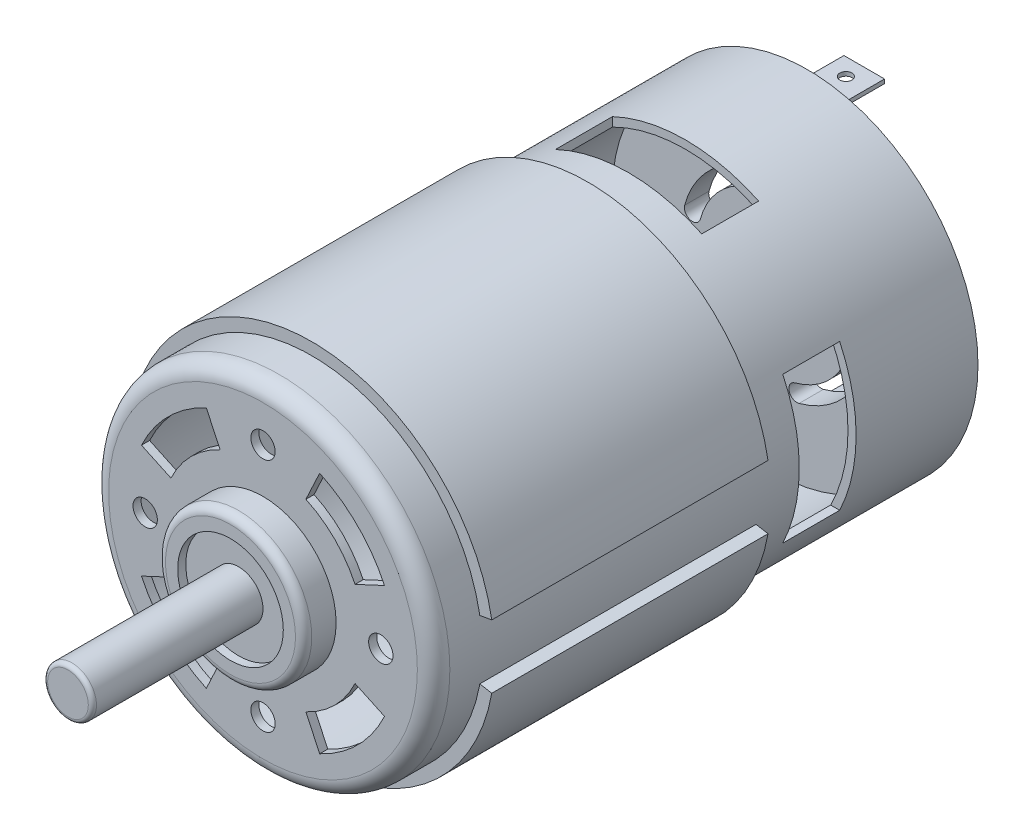
SolidWorks part; units mm, degrees
ref_plane "Front Plane" through (0, 0, 0) normal (0, 0, 1) x (1, 0, 0)
ref_plane "Top Plane" through (0, 0, 0) normal (0, 1, 0) x (1, 0, 0)
ref_plane "Right Plane" through (0, 0, 0) normal (1, 0, 0) x (0, 0, -1)
sketch "Sketch1" plane through (0, 0, 0) normal (0, 0, 1) x (1, 0, 0)
  circle A0 centre (0, 0) radius 21
  dimension "D1" = 42
extrude "Boss-Extrude1" add sketch "Sketch1" against normal blind 67
shell "Shell1" thickness 1 removed face at (21, 0, -67)
fillet "Fillet1" radius 2 1 edges at (21, 0, 0)
sketch "Sketch2" plane through (0, 0, 0) normal (0, 0, 1) x (1, 0, 0)
  line L0 (-19, 0) -> (19, 0) construction
  line L1 (11.3288, 5.2827) -> (13.1415, 6.128) construction
  line L2 (5.2827, 11.3288) -> (6.128, 13.1415) construction
  line L3 (11.3288, 5.2827) -> (14.9541, 6.9732)
  line L4 (5.2827, 11.3288) -> (6.9732, 14.9541)
  line L5 (11.3288, -5.2827) -> (14.9541, -6.9732)
  line L6 (5.2827, -11.3288) -> (6.9732, -14.9541)
  line L7 (-5.2827, -11.3288) -> (-6.9732, -14.9541)
  line L8 (-11.3288, -5.2827) -> (-14.9541, -6.9732)
  line L9 (-11.3288, 5.2827) -> (-14.9541, 6.9732)
  line L10 (-5.2827, 11.3288) -> (-6.9732, 14.9541)
  circle A0 centre (0, 0) radius 19 construction
  circle A1 centre (0, 0) radius 14.5 construction
  circle A2 centre (14.5, 0) radius 1.5
  circle A3 centre (0, -14.5) radius 1.5
  circle A4 centre (-14.5, 0) radius 1.5
  circle A5 centre (0, 14.5) radius 1.5
  arc A7 (11.3288, 5.2827) -> (5.2827, 11.3288) centre (0, 0) ccw
  arc A8 (5.2827, -11.3288) -> (11.3288, -5.2827) centre (0, 0) ccw
  circle A9 centre (0, 0) radius 12.5 construction
  arc A10 (14.9541, 6.9732) -> (6.9732, 14.9541) centre (0, 0) ccw
  arc A11 (6.9732, -14.9541) -> (14.9541, -6.9732) centre (0, 0) ccw
  arc A12 (-11.3288, -5.2827) -> (-5.2827, -11.3288) centre (0, 0) ccw
  arc A13 (-14.9541, -6.9732) -> (-6.9732, -14.9541) centre (0, 0) ccw
  arc A14 (-5.2827, 11.3288) -> (-11.3288, 5.2827) centre (0, 0) ccw
  arc A15 (-6.9732, 14.9541) -> (-14.9541, 6.9732) centre (0, 0) ccw
  point P7 (0, 0)
  point P20 (0, 0)
  point P42 (0, 0)
  dimension "D1" = 29
  dimension "D2" = 3
  dimension "D6" = 16.5
  dimension "D4" = 25
  dimension "D5" = 40
  dimension "D8" = 25
  dimension "D9" = 40
  dimension "D10" = 4
  dimension "D7" = 2
  dimension "D3" = 4
  dimension "D11" = 4
extrude "Cut-Extrude1" cut sketch "Sketch2" against normal up to next
sketch "Sketch3" plane through (0, 0, 0) normal (0, 0, 1) x (1, 0, 0)
  circle A0 centre (0, 0) radius 9
  dimension "D1" = 18
extrude "Boss-Extrude2" add sketch "Sketch3" along normal blind 4
fillet "Fillet2" radius 1 1 edges at (9, 0, 4)
sketch "Sketch4" plane through (0, 0, 4) normal (0, 0, 1) x (1, 0, 0)
  circle A0 centre (0, 0) radius 6.5
  dimension "D1" = 13
extrude "Cut-Extrude2" cut sketch "Sketch4" against normal blind 1
sketch "Sketch5" plane through (0, 0, 3) normal (0, 0, 1) x (1, 0, 0)
  circle A0 centre (0, 0) radius 3
  dimension "D1" = 6
extrude "Boss-Extrude3" add sketch "Sketch5" along normal blind 21
fillet "Fillet3" radius 0.5 1 edges at (3, 0, 24)
ref_plane "Plane1" through (0, 21, 0) normal (0, 1, 0) x (1, 0, 0)
sketch "Sketch6" plane through (0, 21, 0) normal (0, 1, 0) x (1, 0, 0)
  line L0 (21, 67) -> (-21, 67) construction
  line L1 (-9, 52) -> (9, 52)
  line L2 (-9, 52) -> (-9, 45)
  line L3 (-9, 45) -> (9, 45)
  line L4 (9, 52) -> (9, 45)
  line L5 (-9, 52) -> (9, 45) construction
  line L6 (-9, 45) -> (9, 52) construction
  line L7 (-21, 67) -> (-21, 2) construction
  point P0 (0, 48.5)
  dimension "D1" = 18
  dimension "D2" = 7
  dimension "D3" = 15
  dimension "D4" = 21
extrude "Cut-Extrude3" cut sketch "Sketch6" against normal up to surface (3.1394 mm away) up to face at (20, 0, -67)
pattern_circular "CirPattern1" count 4 over 360 about axis through (0, 0, -67) along (0, 0, 1) of "Cut-Extrude3"
sketch "Sketch7" plane through (0, 0, 0) normal (0, 0, 1) x (1, 0, 0)
  circle A0 centre (0, 0) radius 22.5
  circle A1 centre (0, 0) radius 21 construction
  circle A2 centre (0, 0) radius 21
  dimension "D1" = 45
extrude "Boss-Extrude4" add sketch "Sketch7" against normal blind 34 from offset 6 separate body offset against normal yes
sketch "Sketch9" plane through (0, 0, -6) normal (0, 0, 1) x (1, 0, 0)
  line L0 (0, 0) -> (22.5, 0) construction
  line L1 (20.681, 3.6466) -> (22.1582, 3.9071)
  line L2 (20.681, -3.6466) -> (22.1582, -3.9071)
  circle A0 centre (0, 0) radius 22.5 construction
  circle A1 centre (0, 0) radius 21 construction
  arc A2 (22.1582, -3.9071) -> (22.1582, 3.9071) centre (0, 0) ccw
  arc A3 (20.681, -3.6466) -> (20.681, 3.6466) centre (0, 0) ccw
  dimension "D1" = 10
  dimension "D2" = 10
  dimension "D3" = 1.5
  dimension "D4" = 1.5
extrude "Cut-Extrude4" cut sketch "Sketch9" against normal blind 34
sketch "Sketch10" plane through (0, 0, -67) normal (0, 0, -1) x (-1, 0, 0)
  circle A0 centre (0, 0) radius 20 construction
  circle A3 centre (0, 0) radius 20
extrude "Boss-Extrude5" add sketch "Sketch10" against normal blind 2 from offset 2 separate body offset against normal yes
sketch "Sketch11" plane through (0, 0, -65) normal (0, 0, -1) x (-1, 0, 0)
  circle A0 centre (0, 0) radius 15
  dimension "D1" = 30
extrude "Boss-Extrude6" add sketch "Sketch11" along normal blind 1
fillet "Fillet4" radius 1 1 edges at (-15, 0, -66)
sketch "Sketch12" plane through (0, 0, -66) normal (0, 0, -1) x (-1, 0, 0)
  circle A0 centre (0, 0) radius 7.5
  dimension "D1" = 15
extrude "Boss-Extrude7" add sketch "Sketch12" along normal blind 5
sketch "Sketch13" plane through (0, 0, -71) normal (0, 0, -1) x (-1, 0, 0)
  circle A0 centre (0, 0) radius 4
  dimension "D1" = 8
extrude "Boss-Extrude8" add sketch "Sketch13" along normal blind 2
sketch "Sketch14" plane through (0, 0, -73) normal (0, 0, -1) x (-1, 0, 0)
  circle A0 centre (0, 0) radius 3
  dimension "D1" = 6
extrude "Boss-Extrude9" add sketch "Sketch14" along normal blind 5
fillet "Fillet5" radius 0.5 1 edges at (-3, 0, -78)
fillet "Fillet6" radius 1 1 edges at (-4, 0, -71)
fillet "Fillet7" radius 1 1 edges at (-7.5, 0, -71)
sketch "Sketch15" plane through (0, 0, -66) normal (0, 0, -1) x (-1, 0, 0)
  line L0 (0, 0) -> (10.5, 0) construction
  line L1 (0, 0) -> (10.1422, 2.7176) construction
  line L2 (0, 0) -> (2.7176, 10.1422) construction
  arc A0 (10.1422, 2.7176) -> (2.7176, 10.1422) centre (0, 0) ccw construction
  circle A1 centre (0, 0) radius 10.5 construction
  circle A2 centre (10.5, 0) radius 1
  arc A3 (11.1081, 2.9764) -> (2.9764, 11.1081) centre (0, 0) ccw
  arc A4 (9.1763, 2.4588) -> (2.4588, 9.1763) centre (0, 0) ccw
  arc A5 (9.1763, 2.4588) -> (11.1081, 2.9764) centre (10.1422, 2.7176) ccw
  arc A6 (2.9764, 11.1081) -> (2.4588, 9.1763) centre (2.7176, 10.1422) ccw
  arc A7 (2.7176, -10.1422) -> (10.1422, -2.7176) centre (0, 0) ccw construction
  arc A8 (2.9764, -11.1081) -> (11.1081, -2.9764) centre (0, 0) ccw
  arc A9 (2.4588, -9.1763) -> (9.1763, -2.4588) centre (0, 0) ccw
  arc A10 (2.4588, -9.1763) -> (2.9764, -11.1081) centre (2.7176, -10.1422) ccw
  arc A11 (11.1081, -2.9764) -> (9.1763, -2.4588) centre (10.1422, -2.7176) ccw
  arc A12 (-10.1422, -2.7176) -> (-2.7176, -10.1422) centre (0, 0) ccw construction
  arc A13 (-11.1081, -2.9764) -> (-2.9764, -11.1081) centre (0, 0) ccw
  arc A14 (-9.1763, -2.4588) -> (-2.4588, -9.1763) centre (0, 0) ccw
  arc A15 (-9.1763, -2.4588) -> (-11.1081, -2.9764) centre (-10.1422, -2.7176) ccw
  arc A16 (-2.9764, -11.1081) -> (-2.4588, -9.1763) centre (-2.7176, -10.1422) ccw
  arc A17 (-2.7176, 10.1422) -> (-10.1422, 2.7176) centre (0, 0) ccw construction
  arc A18 (-2.9764, 11.1081) -> (-11.1081, 2.9764) centre (0, 0) ccw
  arc A19 (-2.4588, 9.1763) -> (-9.1763, 2.4588) centre (0, 0) ccw
  arc A20 (-2.4588, 9.1763) -> (-2.9764, 11.1081) centre (-2.7176, 10.1422) ccw
  arc A21 (-11.1081, 2.9764) -> (-9.1763, 2.4588) centre (-10.1422, 2.7176) ccw
  circle A22 centre (-10.5, 0) radius 1
  point P9 (7.4246, 7.4246)
  point P19 (7.4246, -7.4246)
  point P26 (-7.4246, -7.4246)
  point P33 (-7.4246, 7.4246)
  point P38 (0, 0)
  point P40 (0, 0)
  dimension "D1" = 21
  dimension "D2" = 2
  dimension "D5" = 1
  dimension "D3" = 15
  dimension "D4" = 75
  dimension "D6" = 4
  dimension "D7" = 2
extrude "Cut-Extrude5" cut sketch "Sketch15" against normal up to next (3 mm away)
sketch "Sketch16" plane through (0, 0, -65) normal (0, 0, -1) x (-1, 0, 0)
  line L0 (-4.5, 19.4872) -> (-4.5, 15.4872)
  line L1 (-4.5, 15.4872) -> (4.5, 15.4872)
  line L2 (4.5, 15.4872) -> (4.5, 19.4872)
  line L3 (4.5, -19.4872) -> (4.5, -15.4872)
  line L4 (4.5, -15.4872) -> (-4.5, -15.4872)
  line L5 (-4.5, -15.4872) -> (-4.5, -19.4872)
  circle A0 centre (0, 0) radius 20 construction
  arc A1 (4.5, 19.4872) -> (-4.5, 19.4872) centre (0, 0) ccw
  arc A3 (-4.5, -19.4872) -> (4.5, -19.4872) centre (0, 0) ccw
  point P7 (0, 15.4872)
  point P14 (0, 0)
  dimension "D1" = 9
  dimension "D2" = 4
  dimension "D3" = 2
extrude "Boss-Extrude10" add sketch "Sketch16" along normal blind 2 separate body
sketch "Sketch17" plane through (0, 0, -67) normal (0, 0, -1) x (-1, 0, 0)
  line L0 (-4.5, 15.4872) -> (4.5, 15.4872) construction
  line L1 (-2.5, 17.7372) -> (2.5, 17.7372)
  line L2 (-2.5, 17.7372) -> (-2.5, 17.2372)
  line L3 (-2.5, 17.2372) -> (2.5, 17.2372)
  line L4 (2.5, 17.7372) -> (2.5, 17.2372)
  line L5 (-2.5, 17.7372) -> (2.5, 17.2372) construction
  line L6 (-2.5, 17.2372) -> (2.5, 17.7372) construction
  line L7 (-4.5, 19.4872) -> (-4.5, 15.4872) construction
  point P0 (0, 17.4872)
  point P8 (0, 15.4872)
  point P12 (-4.5, 17.4872)
  dimension "D1" = 5
  dimension "D2" = 0.5
extrude "Boss-Extrude11" add sketch "Sketch17" along normal blind 7 separate body
sketch "Sketch18" plane through (0, 17.2372, 0) normal (0, -1, 0) x (1, 0, 0)
  circle A0 centre (-0.1411, -71.8837) radius 0.75
  dimension "D1" = 1.5
extrude "Cut-Extrude6" cut sketch "Sketch18" against normal blind 7
pattern_circular "CirPattern2" count 2 over 360 about axis through (0, 0, -67) along (0, 0, 1) of bodies 119
